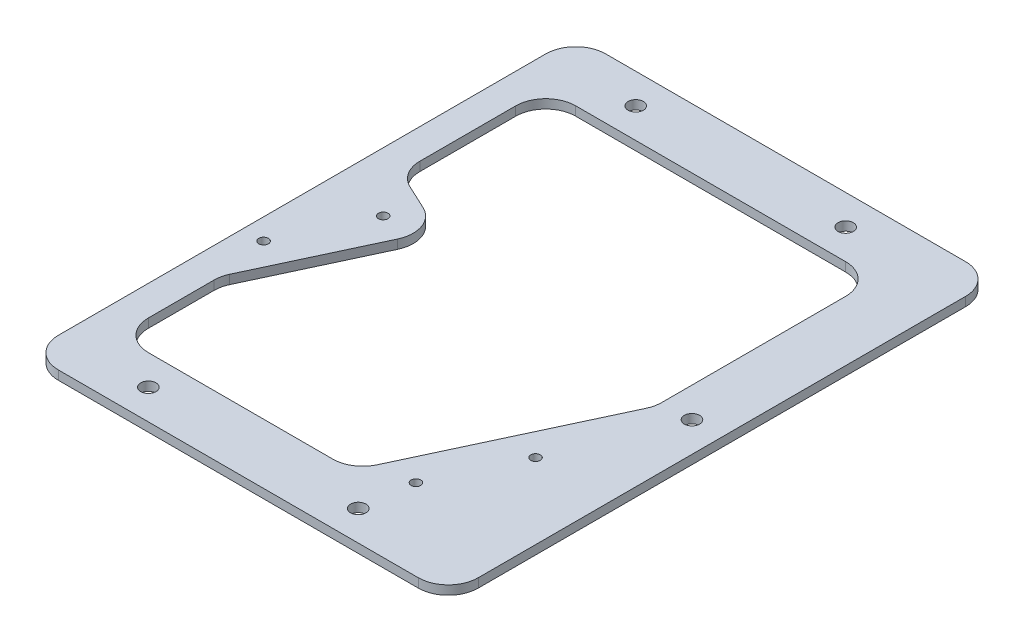
SolidWorks part; units mm, degrees
ref_plane "正面" through (0, 0, 0) normal (0, 0, 1) x (1, 0, 0)
ref_plane "平面" through (0, 0, 0) normal (0, 1, 0) x (1, 0, 0)
ref_plane "右側面" through (0, 0, 0) normal (1, 0, 0) x (0, 0, -1)
sketch "ｽｹｯﾁ1" plane through (0, 0, 0) normal (0, 1, 0) x (1, 0, 0)
  line L0 (-70, 81.25) -> (60, 81.25) construction
  line L1 (-70, 91.25) -> (70, 91.25)
  line L2 (-70, 91.25) -> (-70, -91.25)
  line L3 (-70, -91.25) -> (70, -91.25)
  line L4 (70, 91.25) -> (70, -91.25)
  line L5 (-70, 91.25) -> (70, -91.25) construction
  line L6 (-70, -91.25) -> (70, 91.25) construction
  line L7 (60, 81.25) -> (60, -81.25) construction
  line L8 (60, -81.25) -> (-70, -81.25) construction
  line L9 (-40, 81.25) -> (-40, -81.25) construction
  line L10 (30, 81.25) -> (30, -81.25) construction
  circle A0 centre (-40, 81.25) radius 2.55
  circle A1 centre (30, 81.25) radius 2.55
  circle A2 centre (60, 0) radius 2.55
  circle A3 centre (-40, -81.25) radius 2.55
  circle A4 centre (30, -81.25) radius 2.55
  point P0 (0, 0)
  dimension "D6" = 30
  dimension "D8" = 5.1
  dimension "D1" = 182.5
  dimension "D2" = 140
  dimension "D3" = 10
  dimension "D4" = 10
  dimension "D5" = 10
  dimension "D7" = 40
extrude "ﾎﾞｽ - 押し出し1" add sketch "ｽｹｯﾁ1" along normal blind 3
fillet "ﾌｨﾚｯﾄ1" radius 10 4 edges at (-70, 1.5, -91.25) (70, 1.5, -91.25) (-70, 1.5, 91.25) (70, 1.5, 91.25)
sketch "ｽｹｯﾁ2" plane through (0, 3, 0) normal (0, 1, 0) x (1, 0, 0)
  line L0 (-70, 0) -> (70, -65.2831) construction
  line L1 (-70, 81.25) -> (-70, -81.25) construction
  line L2 (-70, 0) -> (0, 0) construction
  line L3 (70, -81.25) -> (70, 81.25) construction
  line L4 (0, -32.6415) -> (57.7716, 91.25) construction
  line L5 (60, 91.25) -> (-60, 91.25) construction
  line L6 (-50.305, 7.3667) -> (-62.9835, -19.8225) construction
  line L7 (-62.9835, -19.8225) -> (32.1788, -64.1974) construction
  line L8 (32.1788, -64.1974) -> (44.8574, -37.0082) construction
  line L9 (44.8574, -37.0082) -> (-50.305, 7.3667) construction
  line L10 (-62.9835, -19.8225) -> (44.8574, -37.0082) construction
  line L11 (-50.305, 7.3667) -> (32.1788, -64.1974) construction
  circle A0 centre (-50.305, 7.3667) radius 1.6
  circle A1 centre (-62.9835, -19.8225) radius 1.6
  circle A2 centre (44.8574, -37.0082) radius 1.6
  circle A3 centre (32.1788, -64.1974) radius 1.6
  point P16 (-9.0631, -28.4154)
  dimension "D4" = 3.2
  dimension "D1" = 25
  dimension "D2" = 105
  dimension "D3" = 30
  dimension "D5" = 10
extrude "ｶｯﾄ - 押し出し1" cut sketch "ｽｹｯﾁ2" against normal through all
sketch "ｽｹｯﾁ3" plane through (0, 3, 0) normal (0, 1, 0) x (1, 0, 0)
  line L0 (-60, 71.25) -> (50, 71.25)
  line L1 (50, 71.25) -> (50, -2.3177)
  line L2 (50, -2.3177) -> (17.8564, -71.25)
  line L3 (17.8564, -71.25) -> (-60, -71.25)
  line L4 (-60, -71.25) -> (-60, -37.0864)
  line L5 (-60, -37.0864) -> (-37.0157, 12.2036)
  line L6 (-37.0157, 12.2036) -> (-60, 22.9214)
  line L7 (-60, 22.9214) -> (-60, 71.25)
  line L8 (60, 91.25) -> (-60, 91.25) construction
  line L9 (70, -81.25) -> (70, 81.25) construction
  line L10 (-70, 81.25) -> (-70, -81.25) construction
  line L11 (-60, -91.25) -> (60, -91.25) construction
  line L12 (-50.305, 7.3667) -> (-62.9835, -19.8225) construction
  line L13 (44.8574, -37.0082) -> (32.1788, -64.1974) construction
  dimension "D1" = 20
  dimension "D2" = 20
  dimension "D3" = 10
  dimension "D4" = 10
  dimension "D5" = 20
  dimension "D6" = 10
  dimension "D7" = 10
  dimension "D8" = 10
extrude "ｶｯﾄ - 押し出し2" cut sketch "ｽｹｯﾁ3" against normal through all
fillet "ﾌｨﾚｯﾄ2" radius 10 8 edges at (50, 1.5, 2.3177) (17.8564, 1.5, 71.25) (-60, 1.5, 71.25) (-60, 1.5, 37.0864) (-37.0157, 1.5, -12.2036) (-60, 1.5, -22.9214) (50, 1.5, -71.25) (-60, 1.5, -71.25)
